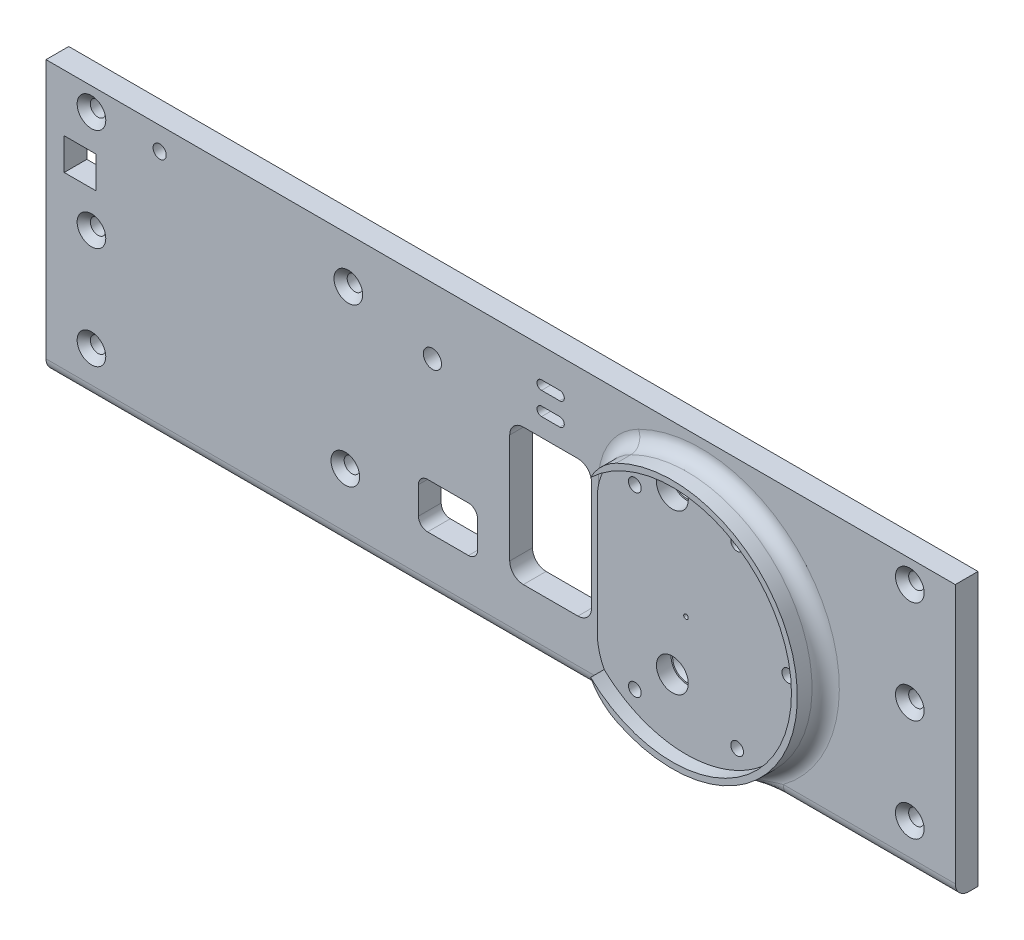
SolidWorks part; units mm, degrees
ref_plane "Front Plane" through (0, 0, 0) normal (0, 0, 1) x (1, 0, 0)
ref_plane "Top Plane" through (0, 0, 0) normal (0, 1, 0) x (1, 0, 0)
ref_plane "Right Plane" through (0, 0, 0) normal (1, 0, 0) x (0, 0, -1)
sketch "Sketch1" plane through (0, 0, 0) normal (0, 0, 1) x (1, 0, 0)
  line L0 (121, 15.3756) -> (121, 39.6244) construction
  line L1 (0, 0) -> (200, 0)
  line L2 (0, 0) -> (0, 60)
  line L3 (0, 60) -> (200, 60)
  line L4 (200, 0) -> (200, 60)
  line L7 (109, 47.5) -> (113, 47.5) construction
  line L8 (105, 42.5) -> (117, 42.5)
  line L9 (102, 39.5) -> (102, 15.5)
  line L10 (105, 12.5) -> (117, 12.5)
  line L11 (120, 39.5) -> (120, 15.5)
  line L12 (121, 15.3756) -> (121, 39.6244) construction
  line L13 (121, 27.5) -> (120, 27.5) construction
  line L18 (109, 48.5) -> (113, 48.5)
  line L19 (109, 46.5) -> (113, 46.5)
  line L20 (111, 42.5) -> (111, 47.5) construction
  line L21 (109, 52.5) -> (113, 52.5) construction
  line L22 (109, 53.5) -> (113, 53.5)
  line L23 (109, 51.5) -> (113, 51.5)
  line L24 (111, 52.5) -> (111, 47.5) construction
  circle A0 centre (144, 27.5) radius 26.5 construction
  circle A2 centre (144, 27.5) radius 0.5
  circle A3 centre (85, 45.5) radius 2
  arc A6 (167.525, 27.5) -> (165.475, 27.5) centre (166.5, 27.5) ccw construction
  arc A7 (154.225, 8.0144) -> (156.275, 8.0144) centre (155.25, 8.0144) ccw construction
  arc A8 (131.725, 8.0144) -> (133.775, 8.0144) centre (132.75, 8.0144) ccw construction
  arc A9 (131.725, 46.9856) -> (133.775, 46.9856) centre (132.75, 46.9856) ccw construction
  arc A10 (156.275, 46.9856) -> (154.225, 46.9856) centre (155.25, 46.9856) ccw construction
  arc A11 (167.525, 27.5) -> (165.475, 27.5) centre (166.5, 27.5) ccw construction
  arc A12 (154.225, 8.0144) -> (156.275, 8.0144) centre (155.25, 8.0144) ccw construction
  arc A13 (131.725, 8.0144) -> (133.775, 8.0144) centre (132.75, 8.0144) ccw construction
  arc A14 (131.725, 46.9856) -> (133.775, 46.9856) centre (132.75, 46.9856) ccw construction
  arc A15 (156.275, 46.9856) -> (154.225, 46.9856) centre (155.25, 46.9856) ccw construction
  circle A16 centre (155.25, 46.9856) radius 1.4
  circle A17 centre (166.5, 27.5) radius 1.4
  circle A18 centre (155.25, 8.0144) radius 1.4
  circle A19 centre (132.75, 8.0144) radius 1.4
  circle A20 centre (132.75, 46.9856) radius 1.4
  arc A21 (102, 15.5) -> (105, 12.5) centre (105, 15.5) ccw
  arc A22 (117, 12.5) -> (120, 15.5) centre (117, 15.5) ccw
  arc A23 (117, 42.5) -> (120, 39.5) centre (117, 39.5) cw
  arc A24 (105, 42.5) -> (102, 39.5) centre (105, 39.5) ccw
  arc A29 (109, 48.5) -> (109, 46.5) centre (109, 47.5) ccw
  arc A30 (113, 46.5) -> (113, 48.5) centre (113, 47.5) ccw
  arc A31 (109, 53.5) -> (109, 51.5) centre (109, 52.5) ccw
  arc A32 (113, 51.5) -> (113, 53.5) centre (113, 52.5) ccw
  point P18 (111, 47.5)
  point P55 (111, 52.5)
  dimension "D1" = 1
  dimension "D2" = 4
  dimension "D5" = 53
  dimension "D9" = 1
  dimension "D12" = 18
  dimension "D13" = 2.8
  dimension "D14" = 30
  dimension "D10" = 3
  dimension "D15" = 4
  dimension "D18" = 5
  dimension "D3" = 59
  dimension "D4" = 18
  dimension "D6" = 85
  dimension "D7" = 200
  dimension "D8" = 60
  dimension "D11" = 1
  dimension "D16" = 2
  dimension "D17" = 5
extrude "Boss-Extrude1" add sketch "Sketch1" along normal blind 5
sketch "Sketch3" plane through (0, 0, 5) normal (0, 0, 1) x (1, 0, 0)
  line L0 (124.5, 40.4615) -> (124.5, 14.5385)
  arc A0 (131.6724, 2.9179) -> (131.6724, 52.0821) centre (144, 27.5) ccw
  arc A1 (124.5, 40.4615) -> (131.6724, 52.0821) centre (137.5, 40.4615) cw
  arc A2 (124.5, 14.5385) -> (131.6724, 2.9179) centre (137.5, 14.5385) ccw
  circle A3 centre (144, 27.5) radius 0.5 construction
  circle A4 centre (132.75, 8.0144) radius 1.4 construction
  circle A5 centre (155.25, 8.0144) radius 1.4 construction
  circle A6 centre (166.5, 27.5) radius 1.4 construction
  circle A7 centre (155.25, 46.9856) radius 1.4 construction
  circle A8 centre (132.75, 46.9856) radius 1.4 construction
  circle A9 centre (144, 27.5) radius 0.5
  circle A10 centre (132.75, 8.0144) radius 1.4
  circle A11 centre (155.25, 8.0144) radius 1.4
  circle A12 centre (166.5, 27.5) radius 1.4
  circle A13 centre (155.25, 46.9856) radius 1.4
  circle A14 centre (132.75, 46.9856) radius 1.4
  dimension "D1" = 13
  dimension "D3" = 27.5
  dimension "D2" = 19.5
extrude "Boss-Extrude2" add sketch "Sketch3" along normal up to surface (3.23 mm away)
fillet "Fillet1" radius 3 5 edges at (126.4375, 7.7106, 5) (124.5, 27.5, 5) (126.4375, 47.2894, 5) (137.6659, 0.7394, 5) (170.7606, 33.8341, 5)
sketch "Sketch8" plane through (0, 0, 5) normal (0, 0, 1) x (1, 0, 0)
  line L0 (10, 55) -> (190, 55) construction
  line L1 (66.5, 50) -> (66.5, 60) construction
  line L2 (200, 60) -> (0, 60) construction
  line L3 (65.8314, 15) -> (66.5, 15) construction
  line L4 (66.5, 15) -> (66.5, 50) construction
  line L5 (66.5, 15) -> (141, 15) construction
  circle A0 centre (190, 10) radius 3 construction
  circle A1 centre (190, 32.5) radius 3 construction
  circle A2 centre (190, 55) radius 3 construction
  circle A3 centre (10, 10) radius 3 construction
  circle A4 centre (10, 32.5) radius 3 construction
  circle A5 centre (10, 55) radius 3 construction
  circle A6 centre (190, 10) radius 3
  circle A7 centre (190, 32.5) radius 3
  circle A8 centre (190, 55) radius 3
  circle A9 centre (10, 10) radius 3
  circle A10 centre (10, 32.5) radius 3
  circle A11 centre (10, 55) radius 3
  circle A12 centre (141, 15) radius 2.1 construction
  circle A13 centre (65.8314, 15) radius 3 construction
  circle A14 centre (141, 15) radius 2.1
  circle A15 centre (65.8314, 15) radius 3
  circle A16 centre (66.5, 15) radius 3
  circle A17 centre (66.5, 50) radius 3 construction
  circle A18 centre (66.5, 50) radius 2.1 construction
  circle A19 centre (66.5, 50) radius 2.1
sketch "Sketch10" plane through (0, 0, 5) normal (0, 0, 1) x (1, 0, 0)
  circle A0 centre (141, 15) radius 3.5
  circle A1 centre (66.5, 15) radius 3.5
  circle A3 centre (141, 50) radius 2.1 construction
  circle A5 centre (66.5, 50) radius 3
  circle A6 centre (141, 50) radius 2.1 construction
  circle A7 centre (141, 50) radius 3.5
  dimension "D1" = 7
  dimension "D2" = 6
extrude "Cut-Extrude2" cut sketch "Sketch10" along normal through all
hole_wizard "CSK for M3 Flat Head Machine Screw1" positions "3DSketch1" profile "Sketch9" countersink size "M3" standard "ANSI Metric" end condition through all
sketch3d "3DSketch1"
  line L2 (141, 50, 5) -> (141, 50, 4.8453) construction
  line L4 (141, 15, 8.23) -> (141, 15, 5) construction
  circle A0 centre (65.8314, 15, 5) radius 3 construction
  circle A1 centre (65.8314, 15, 5) radius 3 construction
  point P0 (10, 55, 5)
  point P3 (10, 32.5, 5)
  point P6 (10, 10, 5)
  point P12 (190, 10, 5)
  point P15 (190, 32.5, 5)
  point P18 (190, 55, 5)
  point P37 (66.5, 50, 5)
  point P85 (141, 50, 5)
  point P95 (141, 15, 5)
  point P107 (65.8314, 15, 5)
  point P109 (65.8314, 15, 8)
  point P111 (65.8314, 15, 8)
  point P115 (65.8314, 15, 5)
  point P117 (65.8314, 15, 5)
  point P119 (65.8314, 15, 5)
  point P121 (65.8314, 15, 5)
  point P123 (65.8314, 15, 5)
  point P130 (65.8314, 15, 5)
sketch "Sketch9" plane through (10, 55, 5) normal (1, 0, 0) x (0, -1, 0)
  line L0 (0, 0) -> (0, 5)
  line L1 (0, 5) -> (1.7, 5)
  line L2 (1.7, 5) -> (1.7, 1.45)
  line L3 (1.7, 1.45) -> (3.15, 0)
  line L5 (3.15, 0) -> (0, 0)
  line L6 (-1.7, 1.45) -> (-3.15, 0) construction
  line L11 (0, -6.35) -> (0, 107.95) construction
  dimension "Thru Hole Dia." = 3.4
  dimension "Thru Hole Depth" = 5
  dimension "Near C'Sink Dia." = 6.3
  dimension "Near C'Sink Angle" = 90
fillet "Fillet2" radius 3 4 edges at (65.4045, 0, 5) (137.4045, 0, 5) (178.5955, 0, 5) (150.5955, 0, 5)
sketch "Sketch13" plane through (0, 0, 5) normal (0, 0, 1) x (1, 0, 0)
  line L0 (0, 60) -> (0, 3) construction
  line L1 (4, 47.5) -> (11, 47.5)
  line L2 (4, 47.5) -> (4, 40.5)
  line L3 (4, 40.5) -> (11, 40.5)
  line L4 (11, 47.5) -> (11, 40.5)
  line L5 (200, 60) -> (0, 60) construction
  circle A2 centre (25, 55) radius 1.45
  circle A3 centre (25, 55) radius 3.5 construction
  dimension "D1" = 2.9
  dimension "D2" = 7
  dimension "D3" = 7
  dimension "D4" = 4
  dimension "D5" = 12.5
extrude "swtich mount hole" cut sketch "Sketch13" against normal through all
sketch "Sketch14" plane through (0, 0, 5) normal (0, 0, 1) x (1, 0, 0)
  line L1 (83.9252, 22) -> (92.9252, 22)
  line L2 (81.9252, 20) -> (81.9252, 14)
  line L3 (83.9252, 12) -> (92.9252, 12)
  line L4 (94.9252, 20) -> (94.9252, 14)
  line L6 (0, 0) -> (200, 0) construction
  arc A0 (92.9252, 12) -> (94.9252, 14) centre (92.9252, 14) ccw
  arc A1 (92.9252, 22) -> (94.9252, 20) centre (92.9252, 20) cw
  arc A2 (81.9252, 14) -> (83.9252, 12) centre (83.9252, 14) ccw
  arc A3 (83.9252, 22) -> (81.9252, 20) centre (83.9252, 20) ccw
  point P8 (94.9252, 12)
  point P11 (94.9252, 22)
  point P16 (81.9252, 22)
  dimension "D3" = 2
  dimension "D1" = 13
  dimension "D2" = 10
  dimension "D4" = 12
extrude "Cut-Extrude3" cut sketch "Sketch14" against normal through all
sketch "Sketch15" plane through (0, 0, 8.23) normal (0, 0, 1) x (1, 0, 0)
  arc A1 (126.015, 8.448) -> (126.015, 46.552) centre (144, 27.5) ccw
  arc A2 (170.2, 27.5) -> (120.8231, 39.7176) centre (144, 27.5) ccw
  arc A3 (170.2, 27.5) -> (120.8231, 39.7176) centre (144, 27.5) ccw construction
  arc A4 (131.6724, 2.9179) -> (149.1738, 0.4911) centre (144, 27.5) ccw
  arc A5 (131.6724, 2.9179) -> (131.6724, 52.0821) centre (144, 27.5) ccw construction
  arc A6 (124.5, 14.5385) -> (131.6724, 2.9179) centre (137.5, 14.5385) ccw construction
  arc A7 (131.6724, 52.0821) -> (124.5, 40.4615) centre (137.5, 40.4615) ccw construction
  arc A8 (126.015, 8.448) -> (131.6724, 2.9179) centre (137.5, 14.5385) ccw
  arc A9 (131.6724, 52.0821) -> (126.015, 46.552) centre (137.5, 40.4615) ccw
  arc A10 (149.1738, 0.4911) -> (131.6724, 52.0821) centre (144, 27.5) ccw
  dimension "D1" = 0.2
extrude "Motor lip" add sketch "Sketch15" along normal blind 3
